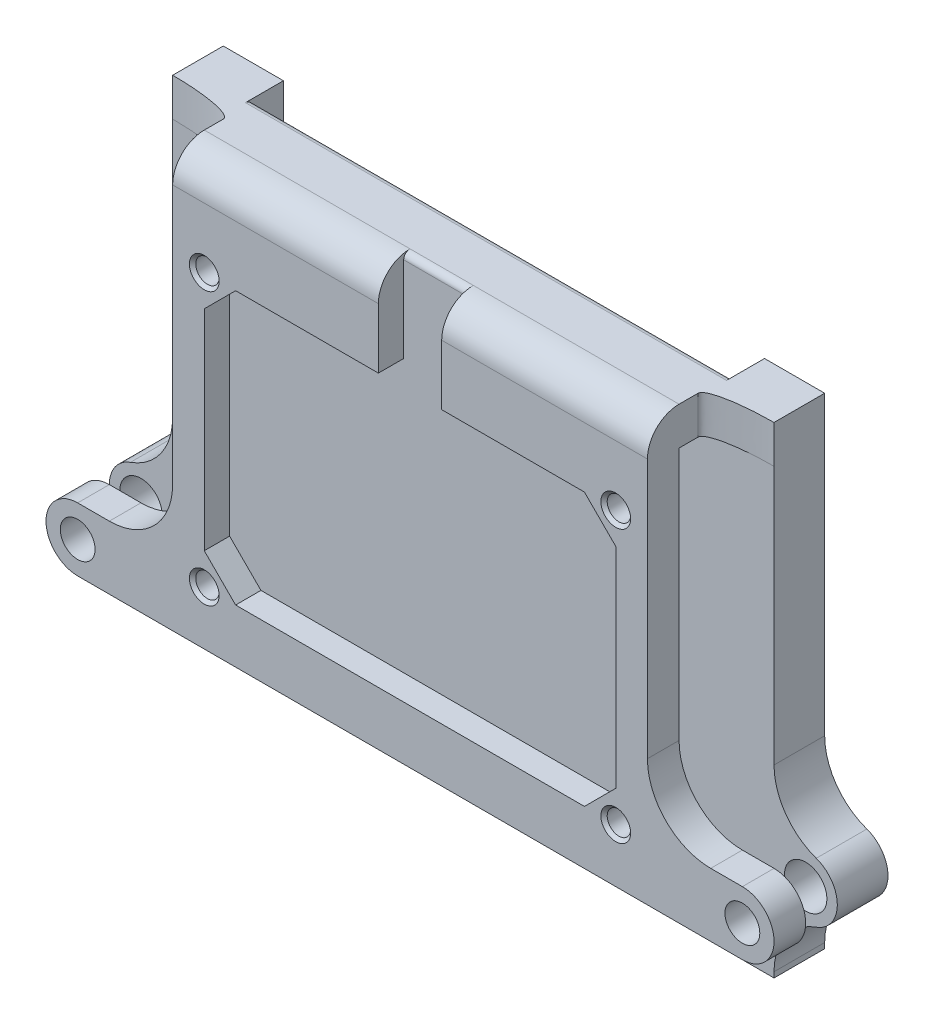
SolidWorks part; units mm, degrees
ref_plane "Front Plane" through (0, 0, 0) normal (0, 0, 1) x (1, 0, 0)
ref_plane "Top Plane" through (0, 0, 0) normal (0, 1, 0) x (1, 0, 0)
ref_plane "Right Plane" through (0, 0, 0) normal (1, 0, 0) x (0, 0, -1)
sketch "Sketch1" plane through (0, 0, 0) normal (0, 0, 1) x (1, 0, 0)
  line L0 (67.462, 80) -> (-67.462, 80) construction
  line L1 (-37.5, 20) -> (37.5, 20)
  line L2 (-37.5, 20) -> (-37.5, 80)
  line L3 (-37.5, 80) -> (37.5, 80)
  line L4 (37.5, 20) -> (37.5, 80)
  line L5 (-37.5, 20) -> (37.5, 80) construction
  line L6 (-37.5, 80) -> (37.5, 20) construction
  line L7 (0, 50) -> (0, 0) construction
  line L9 (-37.5, 80) -> (37.5, 80)
  line L10 (-37.5, 80) -> (-37.5, 86)
  line L11 (-37.5, 86) -> (37.5, 86)
  line L12 (37.5, 80) -> (37.5, 86)
  point P0 (0, 50)
  dimension "D1" = 75
  dimension "D2" = 60
  dimension "D3" = 6
extrude "Boss-Extrude1" add sketch "Sketch1" along normal blind 5 contours L3 L12 L11 L10 | L1 L4 L3 L2 region at (0, 50, 0) region at (0, 83, 0)
sketch "Sketch2" plane through (0, 0, 5) normal (0, 0, 1) x (1, 0, 0)
  line L0 (67.462, 80) -> (-67.462, 80) construction
  line L1 (37.5, 80) -> (-37.5, 80) construction
  line L2 (-37.5, 20) -> (-37.5, 86) construction
  line L3 (37.5, 20) -> (37.5, 86) construction
  line L4 (-37.5, 80) -> (37.5, 20) construction
  line L5 (-32.5, 66.5503) -> (-27.5503, 71.5)
  line L6 (-32.5, 28.5) -> (32.5, 28.5)
  line L7 (-32.5, 28.5) -> (-32.5, 71.5)
  line L8 (-32.5, 71.5) -> (32.5, 71.5)
  line L9 (32.5, 28.5) -> (32.5, 71.5)
  line L10 (-32.5, 28.5) -> (32.5, 71.5) construction
  line L11 (-32.5, 71.5) -> (32.5, 28.5) construction
  line L12 (0, 71.5) -> (0, 28.5) construction
  line L13 (-32.5, 50) -> (32.5, 50) construction
  line L14 (32.5, 66.5503) -> (27.5503, 71.5)
  line L15 (32.5, 33.4497) -> (27.5503, 28.5)
  line L16 (-32.5, 33.4497) -> (-27.5503, 28.5)
  line L17 (-37.5, 86) -> (37.5, 86) construction
  line L18 (-5, 71.5) -> (5, 71.5)
  line L19 (-5, 71.5) -> (-5, 86)
  line L20 (-5, 86) -> (5, 86)
  line L21 (5, 71.5) -> (5, 86)
  line L22 (-5, 71.5) -> (5, 86) construction
  line L23 (-5, 86) -> (5, 71.5) construction
  line L24 (0, 78.75) -> (0, 71.5) construction
  circle A0 centre (-32.5, 71.5) radius 1.85
  circle A1 centre (32.5, 71.5) radius 1.85
  circle A2 centre (32.5, 28.5) radius 1.85
  circle A3 centre (-32.5, 28.5) radius 1.85
  point P2 (0, 50)
  point P31 (0, 78.75)
  line M7 (37.5, 86) -> (-37.5, 86)
  dimension "D3" = 3.7
  dimension "D1" = 65
  dimension "D2" = 43
  dimension "D4" = 45
  dimension "D5" = 3.5
  dimension "D6" = 10
extrude "Cut-Extrude1" cut sketch "Sketch2" against normal blind 4 contours L7 L16 L6 L15 L9 L14 L8 L5 | L8 L21 L19 M7 region at (0, 50, 5) region at (0, 78.75, 5)
extrude "Cut-Extrude2" cut sketch "Sketch2<3>" against normal blind 4.5 contours L8 A0 L7 | L7 A0 L8 | L9 A1 L8 | L8 A1 L9 | L9 A2 L6 | L6 A2 L9 | L7 A3 L6 | L6 A3 L7 region at (-32.7617, 71.7617, 5) region at (-31.7148, 70.7148, 5) region at (-31.7148, 29.2852, 5) region at (-32.7617, 28.2383, 5) region at (31.7148, 29.2852, 5) region at (32.7617, 28.2383, 5) region at (32.7617, 71.7617, 5) region at (31.7148, 70.7148, 5)
sketch "Sketch2<3>" plane through (0, 0, 5) normal (0, 0, 1) x (1, 0, 0) same geometry as "Sketch2"
sketch "Sketch3" plane through (0, 0, 0) normal (0, 0, -1) x (-1, 0, 0)
  line L0 (37.5, 20) -> (37.5, 86) construction
  line L1 (-37.5, 86) -> (37.5, 86)
  line L2 (-37.5, 86) -> (-37.5, 80)
  line L3 (-37.5, 80) -> (37.5, 80)
  line L4 (37.5, 86) -> (37.5, 80)
  line L5 (-67.462, 80) -> (67.462, 80) construction
extrude "Boss-Extrude2" add sketch "Sketch3" along normal blind 5 contours L2 L1 L4 L3
sketch "Sketch4" plane through (0, 0, -5) normal (0, 0, -1) x (-1, 0, 0)
  line L0 (0, 80) -> (0, 48) construction
  line L2 (-47.5, 10) -> (47.5, 10)
  line L3 (-47.5, 10) -> (-47.5, 86)
  line L4 (-37.5, 80) -> (37.5, 80)
  line L5 (37.5, 80) -> (37.5, 86)
  line L6 (37.5, 86) -> (-37.5, 86)
  line L7 (-37.5, 86) -> (-37.5, 80)
  line L8 (-37.5, 80) -> (37.5, 80)
  line L9 (37.5, 80) -> (37.5, 86)
  line L10 (37.5, 86) -> (-37.5, 86)
  line L11 (-37.5, 86) -> (-37.5, 80)
  line L12 (-47.5, 86) -> (47.5, 86)
  line L13 (47.5, 10) -> (47.5, 86)
  line L14 (-47.5, 10) -> (47.5, 86) construction
  line L15 (-47.5, 86) -> (47.5, 10) construction
  line M7 (-37.5, 80) -> (37.5, 80)
  line M8 (37.5, 80) -> (37.5, 86)
  line M9 (37.5, 86) -> (-37.5, 86)
  line M10 (-37.5, 86) -> (-37.5, 80)
  dimension "D2" = 95
  dimension "D3" = 76
  dimension "D1" = 0
extrude "Boss-Extrude3" add sketch "Sketch4" along normal blind 8 contours L2 L13 L12 L3 M7 | M10 M7 M8 M9 region at (0, 45.6736, -5) region at (0, 83, -5)
sketch "Sketch5" plane through (0, 0, -13) normal (0, 0, -1) x (-1, 0, 0)
  line L0 (-47.5, 80) -> (47.5, 10) construction
  line L1 (-67.462, 80) -> (67.462, 80) construction
  line L7 (-67.462, 80) -> (67.462, 80) construction
  line L12 (-47.5, 86) -> (47.5, 86) construction
  line L13 (-38, 10) -> (38, 10)
  line L18 (-47.5, 10) -> (-47.5, 86) construction
  line L19 (-38, 10) -> (-38, 86)
  line L20 (0, 50) -> (0, 45) construction
  line L21 (-41.5, 21) -> (41.5, 21) construction
  line L22 (-41.5, 21) -> (-41.5, 79) construction
  line L23 (-41.5, 79) -> (41.5, 79) construction
  line L24 (41.5, 21) -> (41.5, 79) construction
  line L25 (-41.5, 21) -> (41.5, 79) construction
  line L26 (-41.5, 79) -> (41.5, 21) construction
  line L27 (-38, 86) -> (38, 86)
  line L28 (38, 10) -> (38, 86)
  line L29 (-38, 10) -> (38, 86) construction
  line L30 (-38, 86) -> (38, 10) construction
  line L31 (-47.5, 10) -> (47.5, 10) construction
  circle A0 centre (-41.5, 79) radius 1.85
  circle A1 centre (41.5, 79) radius 1.85
  circle A2 centre (41.5, 21) radius 1.85
  circle A3 centre (-41.5, 21) radius 1.85
  point P4 (0, 45)
  point P13 (0, 50)
  point P14 (0, 48)
  point P29 (0, 50)
  line M13 (47.5, 86) -> (-47.5, 86)
  dimension "D3" = 3.7
  dimension "D1" = 58
  dimension "D2" = 83
  dimension "D4" = 76
  dimension "D7" = 5
extrude "Cut-Extrude3" cut sketch "Sketch5" against normal blind 5 contours L27 M13 region at (0, 48, -13)
extrude "Cut-Extrude4" cut sketch "Sketch5<3>" against normal blind 4.5 contours A0 | A3 | A2 | A1 region at (41.5, 79, -13) region at (-41.5, 79, -13) region at (-41.5, 21, -13) region at (41.5, 21, -13)
sketch "Sketch5<3>" plane through (0, 0, -13) normal (0, 0, -1) x (-1, 0, 0) same geometry as "Sketch5"
fillet "Fillet1" radius 1 2 edges at (0, 86, 1) (0, 86, -8)
fillet "Fillet2" radius 5 2 edges at (21.25, 86, 5) (-21.25, 86, 5)
fillet "Fillet3" radius 2 2 edges at (37.5, 83, -5) (-37.5, 83, -5) second distance 10 first distance on face at (37.5, 64.8622, 0.1479) first distance on face at (-37.5, 64.8622, 0.1479)
sketch "Sketch7" plane through (0, 0, 5) normal (0, 0, 1) x (1, 0, 0)
  line L0 (0, 86) -> (0, 10) construction
  line L1 (37.5, 20) -> (52.5, 20)
  line L2 (37.5, 20) -> (37.5, 30)
  line L3 (37.5, 30) -> (52.5, 30)
  line L4 (52.5, 20) -> (52.5, 30)
  line L5 (47.5, 10) -> (47.5, 80) construction
  line L6 (-5, 86) -> (5, 86) construction
  line L7 (47.5, 10) -> (-47.5, 10) construction
  line L8 (-37.5, 30) -> (-52.5, 30)
  line L9 (-52.5, 20) -> (-52.5, 30)
  line L10 (-37.5, 20) -> (-52.5, 20)
  line L11 (-37.5, 20) -> (-37.5, 30)
  circle A0 centre (52.5, 25) radius 5
  circle A1 centre (52.5, 25) radius 2.75
  circle A2 centre (-52.5, 25) radius 2.75
  circle A3 centre (-52.5, 25) radius 5
  line M9 (37.5, 20) -> (37.5, 81)
  line M23 (-37.5, 81) -> (-37.5, 20)
  dimension "D1" = 10
  dimension "D2" = 5.5
extrude "Boss-Extrude4" add sketch "Sketch7" against normal up to surface (5 mm away) contours A0 L3 L1 M9 | A1 L4 A0 | A1 L4 A0 | L8 A3 L10 M23 | A3 L9 A2 | A3 L9 A2 region at (43.0927, 25, 5) region at (47.6118, 25, 5) region at (52.6118, 21.125, 5) region at (-43.0927, 25, 5) region at (-49.0435, 28.4565, 5) region at (-52.6118, 28.875, 5) up to face at (0, 50, 0)
sketch "Sketch8" plane through (0, 0, -13) normal (0, 0, -1) x (-1, 0, 0)
  line L0 (-52.5, 30) -> (-37.5, 30) construction
  line L1 (-52.5, 30) -> (-47.5, 30)
  line L2 (-47.5, 10) -> (-47.5, 86) construction
  line L3 (52.5, 20) -> (-52.5, 20) construction
  line L4 (-47.5, 20) -> (-52.5, 20)
  line L5 (0, 86) -> (0, 10) construction
  line L6 (-38, 86) -> (38, 86) construction
  line L7 (-38, 10) -> (38, 10) construction
  line L8 (47.5, 20) -> (52.5, 20)
  line L9 (52.5, 30) -> (47.5, 30)
  line L10 (-47.5, 10) -> (-47.5, 86)
  line L11 (47.5, 10) -> (47.5, 86) construction
  line L12 (47.5, 10) -> (47.5, 86)
  arc A0 (-52.5, 30) -> (-52.5, 20) centre (-52.5, 25) ccw construction
  circle A1 centre (-52.5, 25) radius 5
  circle A2 centre (52.5, 25) radius 3.35
  circle A4 centre (-52.5, 25) radius 3.35
  circle A5 centre (52.5, 25) radius 5
  line M7 (-47.5, 86) -> (-47.5, 10)
  dimension "D1" = 6.7
extrude "Boss-Extrude5" add sketch "Sketch8" against normal up to surface (8 mm away) contours A1 L4 M7 | A1 L1 M7 | A1 A4 | L12 A5 L9 | L8 A5 L12 | A5 A2 region at (48.6168, 28.8832, -13) region at (49.0645, 28.4355, -13) region at (48.6168, 21.1168, -13) region at (-48.6168, 21.1168, -13) region at (-49.0645, 21.5645, -13) region at (-48.6168, 28.8832, -13) up to face at (11.875, 27.5, -5)
fillet "Fillet4" radius 10 6 edges at (37.5, 30, 2.5) (47.5, 20, -9) (47.5, 30, -9) (-37.5, 30, 2.5) (-47.5, 30, -9) (-47.5, 20, -9)
chamfer "Chamfer1" distance 0.5 angle 45 10 edges at (-30.65, 28.5, 5) (34.35, 28.5, 5) (34.35, 71.5, 5) (-30.65, 71.5, 5) (49.15, 25, -13) (-55.85, 25, -13) (-43.35, 21, -13) (-43.35, 79, -13) (39.65, 21, -13) (39.65, 79, -13)
